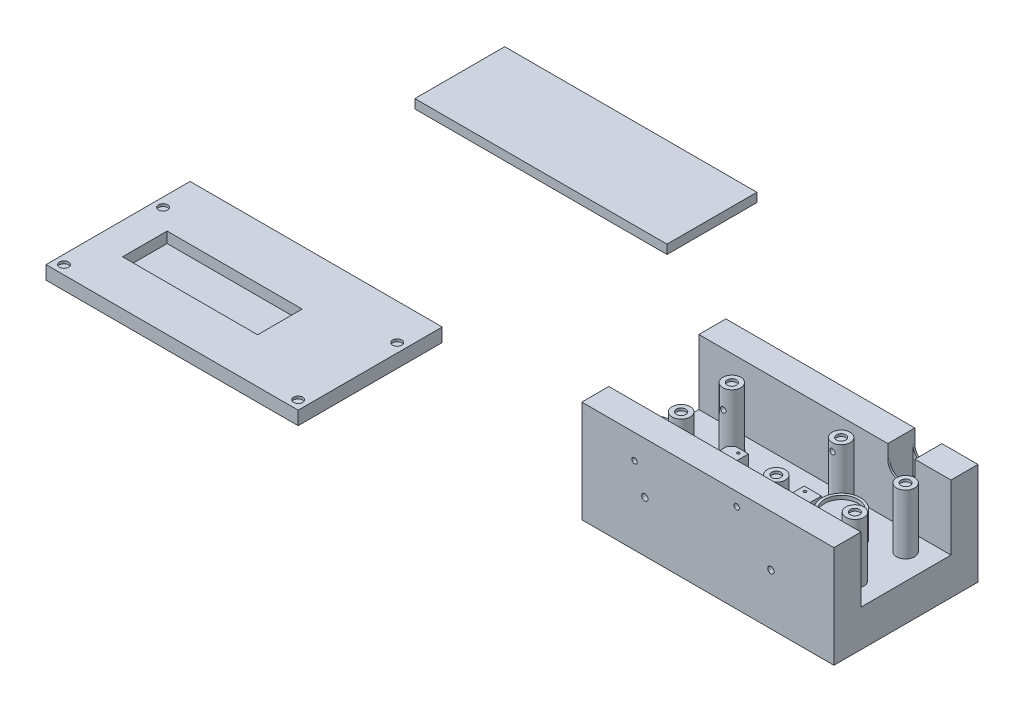
SolidWorks part; units mm, degrees
ref_plane "Front Plane" through (0, 0, 0) normal (0, 0, 1) x (1, 0, 0)
ref_plane "Top Plane" through (0, 0, 0) normal (0, 1, 0) x (1, 0, 0)
ref_plane "Right Plane" through (0, 0, 0) normal (1, 0, 0) x (0, 0, -1)
sketch "Sketch1" plane through (0, 0, 0) normal (0, 1, 0) x (1, 0, 0)
  line L1 (-125, -50) -> (125, -50)
  line L2 (-125, -50) -> (-125, 50)
  line L3 (-125, 50) -> (125, 50)
  line L4 (125, -50) -> (125, 50)
  line L5 (0, 50) -> (0, -50) construction
  line L6 (-125, 0) -> (125, 0) construction
  line L7 (-87.9863, 22.88) -> (-72.79, 22.88)
  line L8 (-91.88, 19.2734) -> (-91.88, -19.2734)
  line L9 (-87.9863, -22.88) -> (-72.79, -22.88)
  line L10 (-72.79, 22.88) -> (-72.79, -22.88)
  line L11 (-10.96, 22.88) -> (8.13, 22.88)
  line L12 (-10.96, 22.88) -> (-10.96, -22.88)
  line L13 (-10.96, -22.88) -> (8.13, -22.88)
  line L14 (8.13, 22.88) -> (8.13, -22.88)
  circle A0 centre (-96.485, 28.15) radius 10
  circle A1 centre (-96.485, -28.15) radius 10
  circle A2 centre (96.485, 28.15) radius 10
  circle A3 centre (96.485, -28.15) radius 10
  circle A4 centre (48.387, 4.8142) radius 21.5
  circle A5 centre (48.387, 4.8142) radius 18.55
  circle A6 centre (-96.485, 28.15) radius 5.17
  circle A7 centre (-96.485, -28.15) radius 5.17
  circle A8 centre (96.485, 28.15) radius 5.17
  circle A9 centre (96.485, -28.15) radius 5.17
  circle A10 centre (-96.485, 28.15) radius 10.5
  circle A11 centre (-96.485, -28.15) radius 10.5
  circle A12 centre (96.485, 28.15) radius 10.5
  circle A13 centre (96.485, -28.15) radius 10.5
  point P0 (0, 0)
  dimension "D3" = 20
  dimension "D6" = 53.46
  dimension "D8" = 43
  dimension "D9" = 37.1
  dimension "D15" = 10.34
  dimension "D16" = 21
  dimension "D17" = 10.34
  dimension "D1" = 250
  dimension "D2" = 100
  dimension "D4" = 192.97
  dimension "D5" = 56.3
  dimension "D7" = 58.31
  dimension "D10" = 19.09
  dimension "D11" = 45.76
  dimension "D12" = 33.12
  dimension "D13" = 114.04
  dimension "D14" = 19.09
extrude "Boss-Extrude1" add sketch "Sketch1" against normal blind 41 contours L1 L4 L3 L2
extrude "Boss-Extrude2" add sketch "Sketch1<4>" along normal blind 12 contours A1 L9 L10 L7 A0 L8 | L14 L11 L12 L13 region at (-82.1271, 0, 0) region at (-1.415, 0, 0)
sketch "Sketch1<4>" plane through (0, 0, 0) normal (0, 1, 0) x (1, 0, 0) same geometry as "Sketch1"
extrude "Boss-Extrude3" add sketch "Sketch1<5>" along normal blind 28.7 contours A4 A5 region at (27.4951, 0, -4.8142)
sketch "Sketch1<5>" plane through (0, 0, 0) normal (0, 1, 0) x (1, 0, 0) same geometry as "Sketch1"
extrude "Boss-Extrude4" add sketch "Sketch1<6>" along normal blind 24.6 contours A5
sketch "Sketch1<6>" plane through (0, 0, 0) normal (0, 1, 0) x (1, 0, 0) same geometry as "Sketch1"
extrude "Cut-Extrude1" cut sketch "Sketch1<9>" against normal blind 5 contours L8 A11 L9 A1 | A1 A7 | A7 | L7 A10 L8 A0 | A0 A6 | A6 | L9 A11 L8 A1 | L8 A10 L7 A0 region at (-86.582, 0, -25.3288) region at (-89.5989, 0, -20.7343) region at (-89.8817, 0, -21.0212) region at (-89.5989, 0, 20.7343) region at (-92.177, 0, 18.9935) region at (-89.8817, 0, 21.0212) region at (-96.485, 0, -28.15) region at (-96.485, 0, 28.15)
sketch "Sketch1<9>" plane through (0, 0, 0) normal (0, 1, 0) x (1, 0, 0) same geometry as "Sketch1"
extrude "Boss-Extrude7" add sketch "Sketch1<10>" along normal blind 66.2 contours A3 A9 | A9 | A2 A8 | A8 | A3 region at (86.7678, 0, -28.15) region at (86.7678, 0, 28.15) region at (96.485, 0, -28.15) region at (96.485, 0, 28.15)
sketch "Sketch1<10>" plane through (0, 0, 0) normal (0, 1, 0) x (1, 0, 0) same geometry as "Sketch1"
extrude "Boss-Extrude8" add sketch "Sketch1<11>" along normal blind 66.2 and the other way up to surface (5 mm away) separate body contours A1 A7 | A7 | A6 | A0 A6 region at (-89.8817, 0, -21.0212) region at (-89.8817, 0, 21.0212) region at (-96.485, 0, -28.15) region at (-96.485, 0, 28.15) other way up to face at (-96.485, -5, -17.65)
sketch "Sketch1<11>" plane through (0, 0, 0) normal (0, 1, 0) x (1, 0, 0) same geometry as "Sketch1"
extrude "Cut-Extrude2" cut sketch "Sketch1<12>" against normal blind 2.75 from surface contours A7 | A6 | A9 | A8 starting at face at (-96.485, 66.2, -18.15)
sketch "Sketch1<12>" plane through (0, 0, 0) normal (0, 1, 0) x (1, 0, 0) same geometry as "Sketch1"
sketch "Sketch3" plane through (0, 12, 0) normal (0, 1, 0) x (1, 0, 0)
  circle A0 centre (-79.2548, 18.1338) radius 1.5
  circle A1 centre (-79.2548, 0.1338) radius 1.5
  circle A2 centre (-5.2548, 18.1338) radius 1.5
  circle A3 centre (-5.2548, 0.1338) radius 1.5
  dimension "D1" = 3
  dimension "D2" = 18
  dimension "D3" = 74
  dimension "D4" = 8.02
  dimension "D5" = 19.93
extrude "Cut-Extrude3" cut sketch "Sketch3" against normal blind 12
sketch "Sketch4" plane through (0, -41, 0) normal (0, -1, 0) x (1, 0, 0)
  line L1 (-120, 30) -> (-39.4754, 30)
  line L2 (-120, 30) -> (-120, -19.5)
  line L3 (-120, -19.5) -> (30, -19.5)
  line L4 (30, 30) -> (30, -19.5)
  line L5 (-125, 50) -> (-125, -50) construction
  line L6 (-125, 50) -> (125, 50) construction
  line L7 (-15.8404, 30) -> (30, 30)
  arc A0 (-15.8404, 30) -> (-39.4754, 30) centre (-27.6579, 30) ccw
  dimension "D1" = 150
  dimension "D2" = 49.5
  dimension "D3" = 20
  dimension "D4" = 5
extrude "Cut-Extrude4" cut sketch "Sketch4" against normal blind 31 contours L1 A0 L7 L4 L3 L2
sketch "Sketch5" plane through (-125, 0, 0) normal (-1, 0, 0) x (0, 0, 1)
  line L0 (-50, 0) -> (-50, -41)
  line L1 (-50, -41) -> (50, -41)
  line L2 (50, -41) -> (50, 0)
  line L3 (50, 0) -> (-50, 0)
extrude "Boss-Extrude9" add sketch "Sketch5" along normal blind 30
sketch "Sketch6" plane through (0, 0, 0) normal (0, 1, 0) x (1, 0, 0)
  line L0 (-130.5, -25.5) -> (-130.5, -47) construction
  line L1 (-155, -50) -> (125, -50) construction
  line L2 (-130.5, -25.5) -> (-155, -25.5) construction
  line L3 (-155, -50) -> (-155, 50) construction
  line L4 (-130.5, -25.5) -> (-152, -25.5) construction
  circle A0 centre (-130.5, -25.5) radius 21.5
  circle A1 centre (-130.5, -25.5) radius 18.55
  dimension "D1" = 43
  dimension "D2" = 37.1
  dimension "D3" = 3
  dimension "D4" = 3
extrude "Boss-Extrude10" add sketch "Sketch6" along normal blind 28.7
sketch "Sketch7" plane through (0, 0, 0) normal (0, 1, 0) x (1, 0, 0)
  circle A0 centre (-130.5, -25.5) radius 18.55
extrude "Boss-Extrude11" add sketch "Sketch7" along normal blind 24.7
sketch "Sketch8" plane through (-155, 0, 0) normal (-1, 0, 0) x (0, 0, 1)
  line L0 (4, 30.377) -> (4, -41) construction
  line L1 (4, 28.7) -> (4, 0) construction
  line L2 (-50, -41) -> (50, -41) construction
  line L3 (50, -41) -> (50, 0) construction
  line L4 (47, 20.3949) -> (47, -41) construction
  line L5 (47, 0) -> (47, 28.7) construction
  dimension "D1" = 46
  dimension "D2" = 3
sketch "Sketch10" plane through (0, 0, 0) normal (0, 1, 0) x (1, 0, 0)
  line L0 (-155, 0) -> (125, 0) construction
  line L1 (-155, -50) -> (-155, 50) construction
  line L2 (125, -50) -> (125, 50) construction
  line L3 (17, -36) -> (17, -46) construction
  line L4 (-155, -50) -> (125, -50) construction
  circle A0 centre (17, -36) radius 10
  circle A1 centre (17, 36) radius 10
  circle A2 centre (17, -36) radius 5.09
  circle A3 centre (17, 36) radius 5.09
  dimension "D1" = 20
  dimension "D4" = 10.18
  dimension "D2" = 4
  dimension "D3" = 108
extrude "Boss-Extrude12" add sketch "Sketch10" along normal blind 66.2
sketch "Sketch11" plane through (0, 0, 0) normal (0, 1, 0) x (1, 0, 0)
  circle A0 centre (17, -36) radius 5.17
  circle A1 centre (17, 36) radius 5.17
  dimension "D1" = 10.34
  dimension "D2" = 10.34
extrude "Boss-Extrude13" add sketch "Sketch11" along normal blind 63.45
sketch "Sketch9" plane through (0, 0, 50) normal (0, 0, 1) x (1, 0, 0)
  line L0 (-96.485, 66.2) -> (-96.485, 0) construction
  line L1 (-86.485, 66.2) -> (-106.485, 66.2) construction
  line L2 (-155, 0) -> (125, 0) construction
  line L3 (-96.485, 0) -> (-96.485, 45) construction
  line L4 (-96.485, 0) -> (-96.485, 57.6) construction
  line L5 (17, 66.2) -> (17, 0) construction
  line L6 (22.09, 66.2) -> (11.91, 66.2) construction
  line L7 (17, 0) -> (17, 57.6) construction
  circle A0 centre (-96.485, 45) radius 3
  circle A1 centre (17, 57.6) radius 3
  dimension "D2" = 6
  dimension "D5" = 6
  dimension "D1" = 45
  dimension "D3" = 57.6
  dimension "D4" = 57.6
extrude "Cut-Extrude5" cut sketch "Sketch9" against normal through all both and the other way through all
sketch "Sketch15" plane through (0, 0, 50) normal (0, 0, 1) x (1, 0, 0)
  line L0 (-155, 15.6) -> (125, 15.6) construction
  line L1 (-155, -41) -> (125, -41)
  line L2 (-155, -41) -> (-155, 72.2)
  line L3 (-155, 72.2) -> (125, 72.2)
  line L4 (125, -41) -> (125, 72.2)
  line L6 (-155, 15.6) -> (-85, 15.6) construction
  line L7 (-85, 15.6) -> (55, 15.6) construction
  circle A0 centre (-85, 15.6) radius 3.5
  circle A1 centre (55, 15.6) radius 3.5
  dimension "D5" = 7
  dimension "D6" = 7
  dimension "D1" = 113.2
  dimension "D2" = 280
  dimension "D3" = 70
  dimension "D4" = 140
extrude "Boss-Extrude17" add sketch "Sketch15" along normal blind 30
sketch "Sketch20" plane through (0, 0, 0) normal (0, 1, 0) x (1, 0, 0)
  line L0 (-605.7799, 235.3036) -> (-325.7799, 235.3036) construction
  line L1 (-605.7799, 285.3036) -> (-325.7799, 285.3036)
  line L2 (-605.7799, 285.3036) -> (-605.7799, 185.3036)
  line L3 (-605.7799, 185.3036) -> (-325.7799, 185.3036)
  line L4 (-325.7799, 285.3036) -> (-325.7799, 185.3036)
  circle A0 centre (-547.2649, 263.4536) radius 5.05
  circle A1 centre (-547.2649, 263.4536) radius 10.05
  circle A2 centre (-433.7799, 271.3036) radius 5.05
  circle A3 centre (-433.7799, 271.3036) radius 10.05
  circle A4 centre (-354.2949, 263.4536) radius 5.05
  circle A5 centre (-354.2949, 263.4536) radius 10.05
  circle A6 centre (-547.2649, 207.1536) radius 5.05
  circle A7 centre (-547.2649, 207.1536) radius 10.05
  circle A8 centre (-433.7799, 199.3036) radius 5.05
  circle A9 centre (-433.7799, 199.3036) radius 10.05
  circle A10 centre (-354.2949, 207.1536) radius 5.05
  circle A11 centre (-354.2949, 207.1536) radius 10.05
  circle A12 centre (-581.2799, 209.8036) radius 18.55
  circle A13 centre (-402.3929, 240.1179) radius 18.55
  dimension "D1" = 10.1
  dimension "D2" = 20.1
  dimension "D3" = 10.1
  dimension "D4" = 20.1
  dimension "D5" = 10.1
  dimension "D6" = 20.1
  dimension "D7" = 37.1
  dimension "D8" = 37.1
extrude "Boss-Extrude18" add sketch "Sketch20" against normal blind 4 separate body contours L2 L0 A13 L4 L1 A1 A3 A5 | L0 L2 L3 L4 A13 A12 A7 A9 A11 region at (-471.0616, 0, -260.7215) region at (-458.7027, 0, -210.2185)
sketch "Sketch21" plane through (0, 0, 0) normal (0, 1, 0) x (1, 0, 0)
  line L0 (-605.7799, 235.3036) -> (-325.7799, 235.3036) construction
  line L1 (-605.7799, 285.3036) -> (-605.7799, 185.3036) construction
  line L2 (-325.7799, 285.3036) -> (-325.7799, 185.3036) construction
  line L4 (-605.7799, 285.3036) -> (-325.7799, 285.3036)
  line L5 (-605.7799, 285.3036) -> (-605.7799, 185.3036)
  line L6 (-605.7799, 185.3036) -> (-325.7799, 185.3036)
  line L7 (-325.7799, 285.3036) -> (-325.7799, 185.3036)
  circle A0 centre (-547.2649, 263.4536) radius 5.17
  circle A1 centre (-433.7799, 271.3036) radius 5.17
  circle A2 centre (-354.2949, 263.4536) radius 5.17
  circle A3 centre (-354.2949, 207.1536) radius 5.17
  circle A4 centre (-433.7799, 199.3036) radius 5.17
  circle A5 centre (-547.2649, 207.1536) radius 5.17
  dimension "D1" = 10.34
  dimension "D2" = 10.34
  dimension "D3" = 10.34
  dimension "D4" = 10.34
  dimension "D5" = 10.34
  dimension "D6" = 10.34
extrude "Boss-Extrude19" add sketch "Sketch21" along normal blind 2.75
sketch "Sketch22" plane through (0, 2.75, 0) normal (0, 1, 0) x (1, 0, 0)
  line L1 (-605.7799, 285.3036) -> (-325.7799, 285.3036)
  line L2 (-605.7799, 285.3036) -> (-605.7799, 185.3036)
  line L3 (-605.7799, 185.3036) -> (-325.7799, 185.3036)
  line L4 (-325.7799, 285.3036) -> (-325.7799, 185.3036)
extrude "Boss-Extrude20" add sketch "Sketch22" along normal blind 3.25
sketch "Sketch23" plane through (0, -41, 0) normal (0, -1, 0) x (1, 0, 0)
  circle A0 centre (-27.6579, 30) radius 11.8175
sketch "Sketch24" plane through (0, -41, 0) normal (0, -1, 0) x (1, 0, 0)
  circle A0 centre (-27.6579, 30) radius 11.8175
extrude "Cut-Extrude9" cut sketch "Sketch24" against normal through all both and the other way through all
sketch "Sketch25" plane through (0, -41, 0) normal (0, -1, 0) x (1, 0, 0)
  line L0 (-155, 80) -> (-155, -50) construction
  line L1 (-155, 80) -> (125, 80)
  line L2 (-155, 80) -> (-155, -50)
  line L3 (-155, -50) -> (125, -50)
  line L4 (125, 80) -> (125, -50)
  line L5 (-120, 30) -> (30, 30)
  line L6 (-120, 30) -> (-120, -19.5)
  line L7 (-120, -19.5) -> (30, -19.5)
  line L8 (30, 30) -> (30, -19.5)
  line L9 (-15, -50) -> (-15, 80) construction
  line L10 (-155, 15) -> (125, 15) construction
  circle A0 centre (-145, 70) radius 5.17
  circle A1 centre (-145, -40) radius 5.17
  circle A2 centre (115, -40) radius 5.17
  circle A3 centre (115, 70) radius 5.17
  dimension "D1" = 10.34
  dimension "D2" = 10
  dimension "D4" = 10.34
  dimension "D5" = 10.34
  dimension "D6" = 10.34
  dimension "D3" = 10
extrude "Cut-Extrude10" cut sketch "Sketch25" against normal blind 2.75 and the other way through all contours A1 | A3 | A2 | A0 region at (-145, -41, 70) region at (-145, -41, -40) region at (115, -41, -40) region at (115, -41, 70)
sketch "Sketch27" plane through (0, -41, 0) normal (0, -1, 0) x (1, 0, 0)
  line L0 (-697.9163, 132.1026) -> (-697.9163, 2.1026) construction
  line L1 (-697.9163, 132.1026) -> (-417.9163, 132.1026)
  line L2 (-697.9163, 132.1026) -> (-697.9163, 2.1026)
  line L3 (-697.9163, 2.1026) -> (-417.9163, 2.1026)
  line L4 (-417.9163, 132.1026) -> (-417.9163, 2.1026)
  line L5 (-662.9163, 82.1026) -> (-512.9163, 82.1026)
  line L6 (-662.9163, 82.1026) -> (-662.9163, 32.6026)
  line L7 (-662.9163, 32.6026) -> (-512.9163, 32.6026)
  line L8 (-512.9163, 82.1026) -> (-512.9163, 32.6026)
  line L9 (-557.9163, 2.1026) -> (-557.9163, 132.1026) construction
  line L10 (-697.9163, 67.1026) -> (-417.9163, 67.1026) construction
  circle A0 centre (-687.9163, 122.1026) radius 5.05
  circle A1 centre (-687.9163, 12.1026) radius 5.05
  circle A2 centre (-427.9163, 12.1026) radius 5.05
  circle A3 centre (-427.9163, 122.1026) radius 5.05
  dimension "D1" = 10.1
  dimension "D2" = 10
  dimension "D3" = 10
extrude "Boss-Extrude21" add sketch "Sketch27" along normal blind 2.75 separate body
sketch "Sketch28" plane through (0, -43.75, 0) normal (0, -1, 0) x (1, 0, 0)
  line L1 (-697.9163, 132.1026) -> (-417.9163, 132.1026)
  line L2 (-697.9163, 132.1026) -> (-697.9163, 2.1026)
  line L3 (-697.9163, 2.1026) -> (-417.9163, 2.1026)
  line L4 (-417.9163, 132.1026) -> (-417.9163, 2.1026)
  line L5 (-662.9163, 82.1026) -> (-512.9163, 82.1026)
  line L6 (-662.9163, 82.1026) -> (-662.9163, 32.6026)
  line L7 (-662.9163, 32.6026) -> (-512.9163, 32.6026)
  line L8 (-512.9163, 82.1026) -> (-512.9163, 32.6026)
extrude "Boss-Extrude22" add sketch "Sketch28" along normal blind 9.25
sketch "Sketch29" plane through (0, -53, 0) normal (0, -1, 0) x (1, 0, 0)
  line L1 (-697.9163, 132.1026) -> (-417.9163, 132.1026)
  line L2 (-697.9163, 132.1026) -> (-697.9163, 2.1026)
  line L3 (-697.9163, 2.1026) -> (-417.9163, 2.1026)
  line L4 (-417.9163, 132.1026) -> (-417.9163, 2.1026)
extrude "Boss-Extrude23" add sketch "Sketch29" along normal blind 3
sketch "Sketch31" plane through (0, 0, -50) normal (0, 0, -1) x (-1, 0, 0)
  line L0 (-69.887, 28.7) -> (-69.887, 0) construction
  line L1 (-125, 72.2) -> (-84.937, 72.2)
  line L2 (-125, 72.2) -> (-125, -41)
  line L3 (-125, -41) -> (155, -41)
  line L4 (155, 72.2) -> (155, -41)
  line L5 (-84.937, 57.15) -> (-84.937, 72.2) construction
  line L6 (-69.887, 28.7) -> (-69.887, 72.2) construction
  line L7 (-69.887, 72.2) -> (-69.887, 57.15) construction
  line L8 (-54.837, 57.15) -> (-54.837, 72.2) construction
  line L9 (-84.937, 57.15) -> (-84.937, 72.2)
  line L10 (-54.837, 57.15) -> (-54.837, 72.2)
  line L11 (-54.837, 72.2) -> (155, 72.2)
  arc A0 (-84.937, 57.15) -> (-54.837, 57.15) centre (-69.887, 57.15) ccw
  dimension "D1" = 15.05
  dimension "D2" = 30.1
sketch "Sketch33" plane through (0, 0, 80) normal (0, 0, 1) x (1, 0, 0)
  circle A0 centre (-96.485, 45) radius 3
  circle A1 centre (17, 57.6) radius 3
  dimension "D1" = 6
  dimension "D2" = 6
extrude "Cut-Extrude11" cut sketch "Sketch33" against normal blind 130
sketch "Sketch34" plane through (-155, 0, 0) normal (-1, 0, 0) x (0, 0, 1)
  line L1 (4, -41) -> (4, -25.5) construction
  line L2 (4, 30.377) -> (4, -41) construction
  circle A0 centre (4, -25.5) radius 3
  dimension "D2" = 6
  dimension "D1" = 15.5
extrude "Cut-Extrude12" cut sketch "Sketch34" against normal blind 40
extrude "Boss-Extrude24" add sketch "Sketch31" along normal blind 30
sketch "Sketch35" plane through (0, 72.2, 0) normal (0, 1, 0) x (1, 0, 0)
  line L0 (69.887, 50) -> (69.887, 80) construction
  line L1 (54.837, 50) -> (84.937, 50) construction
  line L2 (84.937, 80) -> (54.837, 80) construction
  line L3 (69.887, 50) -> (69.887, 52) construction
  line L4 (69.887, 52) -> (54.837, 52)
  line L5 (54.837, 80) -> (54.837, 50) construction
  line L6 (54.837, 52) -> (54.837, 78)
  line L8 (84.937, 80) -> (84.937, 50) construction
  line L9 (84.937, 80) -> (84.937, 52)
  line L10 (84.937, 80) -> (84.937, 50) construction
  line L11 (84.937, 52) -> (69.887, 52)
  line L12 (54.837, 78) -> (84.937, 78)
  line L13 (84.937, 78) -> (84.937, 52)
  dimension "D1" = 2
  dimension "D2" = 26
extrude "Cut-Extrude13" cut sketch "Sketch35" against normal blind 45 contours L12 L6 L4 L11 L9 region at (69.887, 72.2, -65)
sketch "Sketch36" plane through (0, 0, 2.1026) normal (0, 0, -1) x (-1, 0, 0)
  line L1 (417.9163, -41) -> (697.9163, -41)
  line L2 (417.9163, -41) -> (417.9163, -56)
  line L3 (417.9163, -56) -> (697.9163, -56)
  line L4 (697.9163, -41) -> (697.9163, -56)
extrude "Boss-Extrude25" add sketch "Sketch36" along normal blind 30
sketch "Sketch37" plane through (0, 0, -185.3036) normal (0, 0, 1) x (1, 0, 0)
  line L1 (-605.7799, 6) -> (-325.7799, 6)
  line L2 (-605.7799, 6) -> (-605.7799, -4)
  line L3 (-605.7799, -4) -> (-325.7799, -4)
  line L4 (-325.7799, 6) -> (-325.7799, -4)
extrude "Cut-Extrude14" cut sketch "Sketch37" against normal blind 0.1
sketch "Sketch38" plane through (0, 0, -285.3036) normal (0, 0, -1) x (-1, 0, 0)
  line L1 (325.7799, 6) -> (605.7799, 6)
  line L2 (325.7799, 6) -> (325.7799, -4)
  line L3 (325.7799, -4) -> (605.7799, -4)
  line L4 (605.7799, 6) -> (605.7799, -4)
extrude "Cut-Extrude15" cut sketch "Sketch38" against normal blind 0.1
sketch "Sketch39" plane through (0, 72.2, 0) normal (0, 1, 0) x (1, 0, 0)
  line L0 (-96.485, 38.65) -> (-96.485, -38.65) construction
  circle A0 centre (-96.485, 28.15) radius 10.5 construction
  arc A1 (-87.4033, 22.88) -> (-91.88, 18.7137) centre (-96.485, 28.15) ccw construction
  circle A2 centre (-96.485, -28.15) radius 10.5 construction
sketch "Sketch40" plane through (0, 0, 0) normal (0, 0, 1) x (1, 0, 0)
  line L1 (-42.9021, 41) -> (69.887, 41) construction
  line L2 (-55.9548, 41) -> (-28.5548, 41) construction
  line L3 (-72.79, 0) -> (-91.9764, 0) construction
  line L4 (-155, 0) -> (125, 0) construction
  line L5 (-82.3832, 0) -> (-82.3832, 43) construction
  line L6 (-82.3832, 43) -> (-82.3832, 26.65) construction
  dimension "D1" = 43
  dimension "D2" = 16.35
